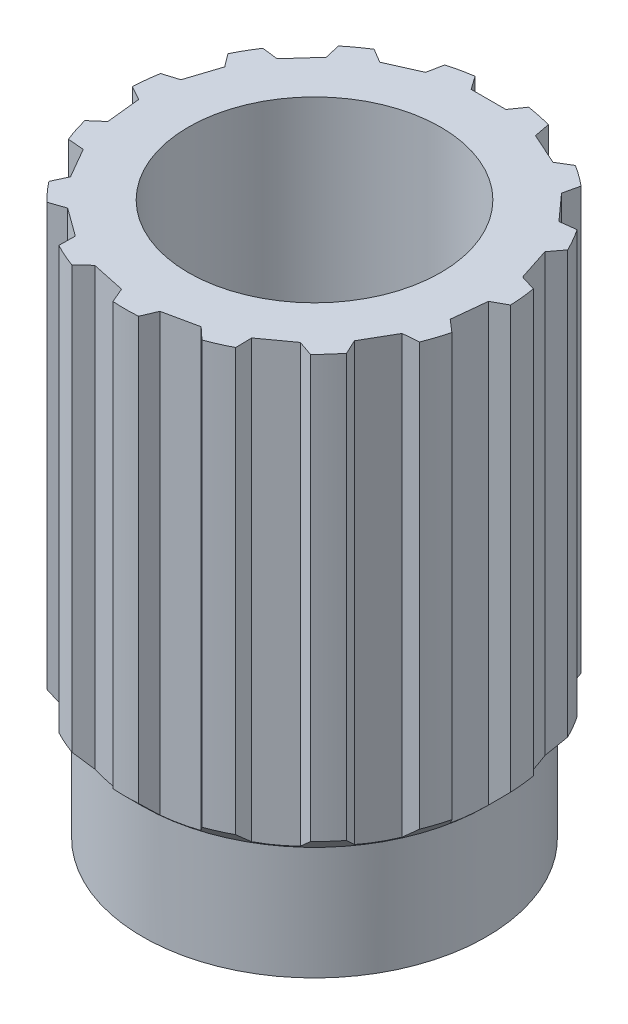
SolidWorks part; units mm, degrees
material "Laiton"
ref_plane "Plan de face" through (0, 0, 0) normal (0, 0, 1) x (1, 0, 0)
ref_plane "Plan de dessus" through (0, 0, 0) normal (0, 1, 0) x (1, 0, 0)
ref_plane "Plan de droite" through (0, 0, 0) normal (1, 0, 0) x (0, 0, -1)
sketch "Esquisse1" plane through (0, 0, 0) normal (0, 1, 0) x (1, 0, 0)
  circle A0 centre (0, 0) radius 4.35
  circle A1 centre (0, 0) radius 2.9
  dimension "D1" = 8.7
  dimension "D2" = 5.8
extrude "Boss.-Extru.1" add sketch "Esquisse1" along normal blind 12.7
sketch "Esquisse2" plane through (0, 0, 0) normal (0, -1, 0) x (1, 0, 0)
  circle A0 centre (0, 0) radius 3.95
  dimension "D1" = 7.9
extrude "Enlèv. mat.-Extru.1" cut sketch "Esquisse2" against normal blind 2 flip side to cut
chamfer "Chanfrein1" distance 1 angle 45 1 edges at (0, 2, -4.35)
sketch "Esquisse3" plane through (0, 12.7, 0) normal (0, 1, 0) x (1, 0, 0)
  line L0 (0, 0) -> (0, 4.8569) construction
  line L1 (1, 4.8569) -> (-1, 4.8569)
  line L2 (-1, 4.8569) -> (-0.4, 4)
  line L3 (-0.4, 4) -> (0.4, 4)
  line L4 (1, 4.8569) -> (0.4, 4)
  line L5 (2.889, 4.0303) -> (1.0619, 4.8437)
  line L6 (1.0619, 4.8437) -> (1.2615, 3.8169)
  line L7 (1.2615, 3.8169) -> (1.9924, 3.4915)
  line L8 (2.889, 4.0303) -> (1.9924, 3.4915)
  line L9 (4.2785, 2.5067) -> (2.9402, 3.993)
  line L10 (2.9402, 3.993) -> (2.7049, 2.9738)
  line L11 (2.7049, 2.9738) -> (3.2402, 2.3793)
  line L12 (4.2785, 2.5067) -> (3.2402, 2.3793)
  line L13 (4.9282, 0.5498) -> (4.3102, 2.4519)
  line L14 (4.3102, 2.4519) -> (3.6806, 1.6165)
  line L15 (3.6806, 1.6165) -> (3.9278, 0.8556)
  line L16 (4.9282, 0.5498) -> (3.9278, 0.8556)
  line L17 (4.7258, -1.5022) -> (4.9348, 0.4868)
  line L18 (4.9348, 0.4868) -> (4.0199, -0.0203)
  line L19 (4.0199, -0.0203) -> (3.9363, -0.8159)
  line L20 (4.7258, -1.5022) -> (3.9363, -0.8159)
  line L21 (3.7062, -3.2945) -> (4.7062, -1.5624)
  line L22 (4.7062, -1.5624) -> (3.6641, -1.6536)
  line L23 (3.6641, -1.6536) -> (3.2641, -2.3464)
  line L24 (3.7062, -3.2945) -> (3.2641, -2.3464)
  line L25 (2.0458, -4.5171) -> (3.6638, -3.3415)
  line L26 (3.6638, -3.3415) -> (2.6747, -3.001)
  line L27 (2.6747, -3.001) -> (2.0275, -3.4712)
  line L28 (2.0458, -4.5171) -> (2.0275, -3.4712)
  line L29 (0.0317, -4.9587) -> (1.988, -4.5428)
  line L30 (1.988, -4.5428) -> (1.2229, -3.8294)
  line L31 (1.2229, -3.8294) -> (0.4404, -3.9958)
  line L32 (0.0317, -4.9587) -> (0.4404, -3.9958)
  line L33 (-1.988, -4.5428) -> (-0.0317, -4.9587)
  line L34 (-0.0317, -4.9587) -> (-0.4404, -3.9958)
  line L35 (-0.4404, -3.9958) -> (-1.2229, -3.8294)
  line L36 (-1.988, -4.5428) -> (-1.2229, -3.8294)
  line L37 (-3.6638, -3.3415) -> (-2.0458, -4.5171)
  line L38 (-2.0458, -4.5171) -> (-2.0275, -3.4712)
  line L39 (-2.0275, -3.4712) -> (-2.6747, -3.001)
  line L40 (-3.6638, -3.3415) -> (-2.6747, -3.001)
  line L41 (-4.7062, -1.5624) -> (-3.7062, -3.2945)
  line L42 (-3.7062, -3.2945) -> (-3.2641, -2.3464)
  line L43 (-3.2641, -2.3464) -> (-3.6641, -1.6536)
  line L44 (-4.7062, -1.5624) -> (-3.6641, -1.6536)
  line L45 (-4.9348, 0.4868) -> (-4.7258, -1.5022)
  line L46 (-4.7258, -1.5022) -> (-3.9363, -0.8159)
  line L47 (-3.9363, -0.8159) -> (-4.0199, -0.0203)
  line L48 (-4.9348, 0.4868) -> (-4.0199, -0.0203)
  line L49 (-4.3102, 2.4519) -> (-4.9282, 0.5498)
  line L50 (-4.9282, 0.5498) -> (-3.9278, 0.8556)
  line L51 (-3.9278, 0.8556) -> (-3.6806, 1.6165)
  line L52 (-4.3102, 2.4519) -> (-3.6806, 1.6165)
  line L53 (-2.9402, 3.993) -> (-4.2785, 2.5067)
  line L54 (-4.2785, 2.5067) -> (-3.2402, 2.3793)
  line L55 (-3.2402, 2.3793) -> (-2.7049, 2.9738)
  line L56 (-2.9402, 3.993) -> (-2.7049, 2.9738)
  line L57 (-1.0619, 4.8437) -> (-2.889, 4.0303)
  line L58 (-2.889, 4.0303) -> (-1.9924, 3.4915)
  line L59 (-1.9924, 3.4915) -> (-1.2615, 3.8169)
  line L60 (-1.0619, 4.8437) -> (-1.2615, 3.8169)
  point P7 (0, 4)
  dimension "D1" = 4
  dimension "D2" = 55
  dimension "D4" = 2
  dimension "D5" = 0.8
  dimension "D3" = 15
extrude "Enlèv. mat.-Extru.2" cut sketch "Esquisse3" against normal through all
